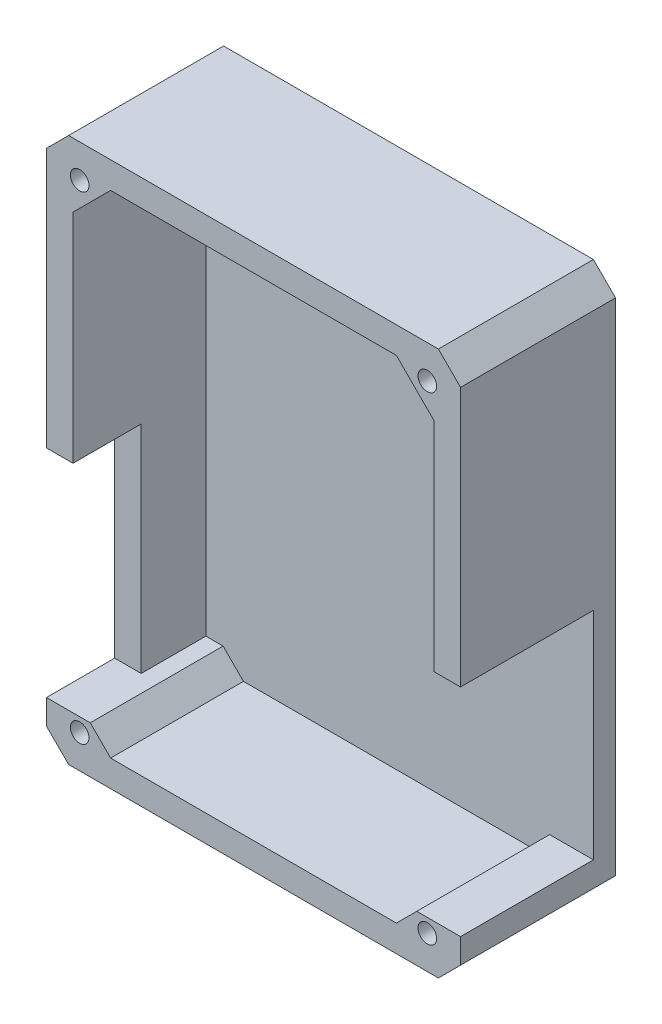
SolidWorks part; units mm, degrees
ref_plane "Front Plane" through (0, 0, 0) normal (0, 0, 1) x (1, 0, 0)
ref_plane "Top Plane" through (0, 0, 0) normal (0, 1, 0) x (1, 0, 0)
ref_plane "Right Plane" through (0, 0, 0) normal (1, 0, 0) x (0, 0, -1)
sketch "Sketch1" plane through (0, 0, 0) normal (0, 0, 1) x (1, 0, 0)
  line L12 (-46.75, -33) -> (46.75, -33)
  line L13 (-46.75, -33) -> (-46.75, 90)
  line L14 (-46.75, 90) -> (46.75, 90)
  line L15 (46.75, -33) -> (46.75, 90)
  dimension "D1" = 123
  dimension "D2" = 93.5
extrude "Boss-Extrude1" add sketch "Sketch1" along normal blind 5
sketch "Sketch3" plane through (0, 0, 5) normal (0, 0, 1) x (1, 0, 0)
  line L0 (-46.75, 26.4) -> (-40.75, 26.4)
  line L1 (-46.75, 90) -> (-46.75, -33) construction
  line L2 (-40.75, 26.4) -> (-40.75, 84)
  line L3 (-40.75, 84) -> (40.75, 84)
  line L4 (40.75, 84) -> (40.75, 26.4)
  line L5 (40.75, 26.4) -> (46.75, 26.4)
  line L6 (46.75, -33) -> (46.75, 90) construction
  line L7 (46.75, 26.4) -> (46.75, 90)
  line L8 (46.75, 90) -> (-46.75, 90)
  line L9 (-46.75, 90) -> (-46.75, 26.4)
  line L10 (-46.75, -33) -> (-46.75, -22.4)
  line L11 (-46.75, -22.4) -> (-40.75, -22.4)
  line L12 (-40.75, -22.4) -> (-40.75, -27)
  line L13 (-40.75, -27) -> (40.75, -27)
  line L14 (40.75, -27) -> (40.75, -22.4)
  line L15 (40.75, -22.4) -> (46.75, -22.4)
  line L16 (46.75, -22.4) -> (46.75, -33)
  line L17 (46.75, -33) -> (-46.75, -33)
  line L18 (0, -33) -> (0, 90) construction
  line L19 (-40.75, 75.5147) -> (-32.2647, 84)
  line L20 (40.75, 75.5147) -> (32.2647, 84)
  line L21 (0, 28.5) -> (6.3358, 28.5) construction
  line L22 (-40.75, -18.5147) -> (-32.2647, -27)
  line L23 (40.75, -18.5147) -> (32.2647, -27)
  line L24 (-40.75, -22.4) -> (-36.8647, -22.4)
  line L25 (40.75, -22.4) -> (36.8647, -22.4)
  line M9 (-46.75, 90) -> (-46.75, -33)
  line M10 (-46.75, -33) -> (46.75, -33)
  line M11 (46.75, -33) -> (46.75, 90)
  line M12 (46.75, 90) -> (-46.75, 90)
  dimension "D1" = 6
  dimension "D2" = 6
  dimension "D3" = 6
  dimension "D4" = 6
  dimension "D5" = 6
  dimension "D6" = 6
  dimension "D7" = 48.8
  dimension "D8" = 48.8
  dimension "D9" = 10.6
  dimension "D10" = 10.6
  dimension "D11" = 45
  dimension "D12" = 12
extrude "Boss-Extrude2" add sketch "Sketch3" along normal blind 30 contours L15 L14 L13 L12 L11 M9 M10 M11 | L24 L12 L13 L22 | L14 L25 L23 L13 | L4 L5 L0 L2 L3 M11 M12 M9 | L20 L4 L3 | L2 L19 L3 region at (-45.6192, 58.2, 5) region at (0, -29.5252, 5) region at (-37.9216, 81.1716, 5) region at (-37.5148, -24.9851, 5) region at (37.9216, 81.1716, 5) region at (37.5148, -24.9851, 5)
chamfer "Chamfer1" distance 5 angle 45 4 edges at (46.75, 90, 17.5) (46.75, -33, 17.5) (-46.75, -33, 17.5) (-46.75, 90, 17.5)
sketch "Sketch4" plane through (0, 0, 5) normal (0, 0, 1) x (1, 0, 0)
  line L1 (-46.75, 26.4) -> (-40.75, 26.4)
  line L2 (-46.75, 26.4) -> (-46.75, -22.4)
  line L3 (-46.75, -22.4) -> (-40.75, -22.4)
  line L4 (-40.75, 26.4) -> (-40.75, -22.4)
extrude "Boss-Extrude3" add sketch "Sketch4" along normal blind 14.6
sketch "Sketch5" plane through (0, 0, 35) normal (0, 0, 1) x (1, 0, 0)
  line L2 (0, 90) -> (0, 63.5343) construction
  line L3 (-46.75, -28) -> (-46.75, 85) construction
  line L4 (-46.75, 28.5) -> (-29.8219, 28.5) construction
  line L5 (41.75, 90) -> (-41.75, 90) construction
  circle A0 centre (-39.25, 82.5) radius 2.1
  circle A1 centre (-39.25, -25.5) radius 2.1
  circle A2 centre (39.25, 82.5) radius 2.1
  circle A3 centre (39.25, -25.5) radius 2.1
  dimension "D1" = 7.5
  dimension "D2" = 4.2
  dimension "D3" = 7.5
extrude "Cut-Extrude1" cut sketch "Sketch5" against normal blind 3.5
sketch "Sketch6" plane through (0, 0, 0) normal (0, 0, -1) x (-1, 0, 0)
  line L0 (0, -33) -> (0, 49.1578) construction
  line L1 (41.75, -33) -> (-41.75, -33) construction
  line L2 (-33.3074, -33) -> (-33.3074, 32) construction
  circle A0 centre (-33.3074, -24) radius 2.1
  circle A1 centre (-33.3074, 32) radius 2.1
  circle A2 centre (33.3074, 32) radius 2.1
  circle A3 centre (33.3074, -24) radius 2.1
  dimension "D1" = 4.2
  dimension "D2" = 4.2
  dimension "D3" = 9
  dimension "D4" = 56
extrude "Cut-Extrude2" cut sketch "Sketch6" against normal blind 3.5
